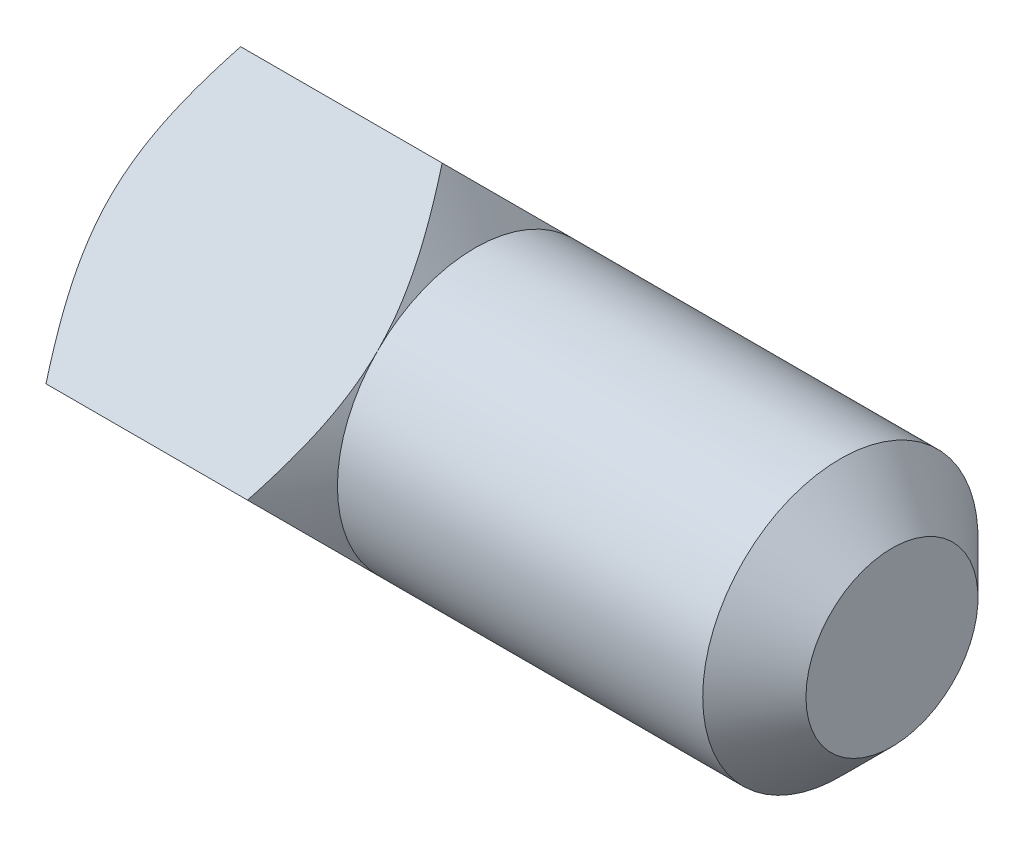
SolidWorks part; units mm, degrees
ref_plane "Front Plane" through (0, 0, 0) normal (0, 0, 1) x (1, 0, 0)
ref_plane "Top Plane" through (0, 0, 0) normal (0, 1, 0) x (1, 0, 0)
ref_plane "Right Plane" through (0, 0, 0) normal (1, 0, 0) x (0, 0, -1)
sketch "BaseHeadSke" plane through (0, 0, 0) normal (1, 0, 0) x (0, 0, -1)
  line L0 (0, 0) -> (14.1701, 0) construction
  line L1 (0, 0) -> (0, 11.9761) construction
  line L2 (0, 2.8284) -> (2.8284, 0)
  line L3 (0, -2.8284) -> (2.8284, 0)
  line L4 (0, 2.8284) -> (-2.8284, 0)
  line L5 (0, -2.8284) -> (-2.8284, 0)
  dimension "Width_flats" = 4
  dimension "Angle" = 45
extrude "BaseHead" add sketch "BaseHeadSke" along normal blind 4
sketch "HeadChamferSke" plane through (0, 0, 0) normal (0, 0, 1) x (1, 0, 0)
  line L0 (0, 0) -> (6.1973, 0) construction
  line L1 (2, 2.8284) -> (2, -3.5627) construction
  line L2 (4, 2.8284) -> (0, 2.8284) construction
  line L3 (0, 2.8284) -> (0, 1.9)
  line L4 (0, 2.8284) -> (0.536, 2.8284)
  line L5 (0.536, 2.8284) -> (0, 1.9)
  line L6 (0, 2.8284) -> (0, 0) construction
  line L7 (3.464, 2.8284) -> (4, 1.9)
  line L8 (4, 2.8284) -> (3.464, 2.8284)
  line L9 (4, 2.8284) -> (4, 1.9)
  dimension "Head_chamfer" = 3.8
  dimension "Angle" = 30
revolve "HeadChamfer" cut sketch "HeadChamferSke" angle 360 about L0
sketch "BodySke" plane through (0, 0, 0) normal (0, 0, 1) x (1, 0, 0)
  line L0 (0, 0) -> (13.1857, 0) construction
  line L1 (4, -1.9) -> (4, 1.9) construction
  line L2 (4, 0) -> (4, 1.9) construction
  line L3 (3.464, 2) -> (10, 2)
  line L4 (10, 2) -> (10, 0)
  line L5 (4, 1.9) -> (4, 2) construction
  line L6 (3.464, 2) -> (3.464, 0)
  line L7 (3.464, 0) -> (10, 0)
  line L8 (9.65, -0.6243) -> (9.65, 3.2323) construction
  point P9 (3.464, 1.61)
  dimension "Minor_dia" = 3.22
  dimension "Advance" = 0.7
revolve "BaseBody" add sketch "BodySke" angle 360 about L0
cosmetic thread "ThreadCosmetic" [suppressed] parameters "Minor_dia"=3.22
sketch "ChamferEndSke" plane through (0, 0, 0) normal (0, 0, 1) x (1, 0, 0)
  line L0 (0, 0) -> (11.9528, 0) construction
  line L1 (10, 2) -> (10, 1.25)
  line L2 (10, 1.25) -> (9.25, 2)
  line L3 (9.25, 2) -> (10, 2)
  line L4 (10, 2) -> (3.9423, 2) construction
  line L5 (10, -2) -> (10, 2) construction
  dimension "D1" = 45
revolve "ChamferEnd" cut sketch "ChamferEndSke" angle 360 about L0
sketch "ThdSchSke" plane through (0, 0, 0) normal (0, 0, 1) x (1, 0, 0)
  line L0 (8.55, 2.4503) -> (8.55, 2)
  line L1 (8.55, 2.4503) -> (9.0003, 2.4503)
  line L2 (9.0003, 2.4503) -> (9.0003, 2)
  line L3 (9.0003, 2) -> (8.7752, 1.61)
  line L4 (8.7752, 1.61) -> (8.55, 2)
  line L5 (0, 0) -> (11.8711, 0) construction
  line L6 (9.25, 2) -> (3.9423, 2) construction
  dimension "D1" = 0.7
revolve "ThreadSchematic" [suppressed] cut sketch "ThdSchSke" angle 360 about L5
pattern_linear "ThdSchPat" [suppressed] count 6 of bodies 105
equation "\"Minor_dia@ThreadCosmetic\" = \"Minor_dia@BodySke\""
equation "\"D1@ThdSchSke\" = \"Advance@BodySke\""
equation "\"Advance@ThdSchPat\" = \"Advance@BodySke\""
equation "\"D1@ThdSchPat\" =  int( (  \"Length@BodySke\" -  ( \"Diameter@BodySke\" - \"End_chamfer@ChamferEndSke\" )  / 2 )  / \"Advance@ThdSchPat\" )  - 1"
